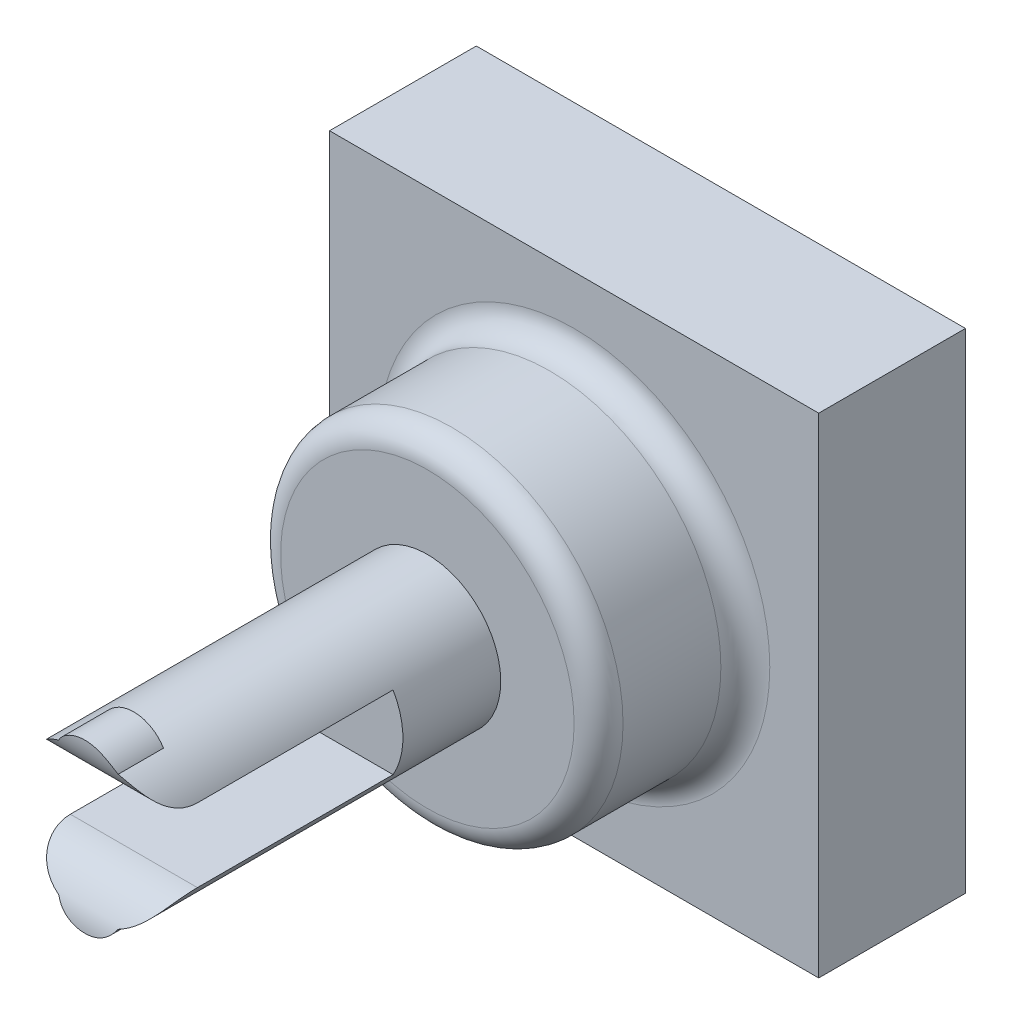
SolidWorks part; units mm, degrees
ref_plane "Plan de face" through (0, 0, 0) normal (0, 0, 1) x (1, 0, 0)
ref_plane "Plan de dessus" through (0, 0, 0) normal (0, 1, 0) x (1, 0, 0)
ref_plane "Plan de droite" through (0, 0, 0) normal (1, 0, 0) x (0, 0, -1)
sketch "Esquisse1" plane through (0, 0, 0) normal (0, 0, 1) x (1, 0, 0)
  line L1 (-5, -5) -> (5, -5)
  line L2 (-5, -5) -> (-5, 5)
  line L3 (-5, 5) -> (5, 5)
  line L4 (5, -5) -> (5, 5)
  line L5 (-5, -5) -> (5, 5) construction
  line L6 (-5, 5) -> (5, -5) construction
  point P0 (0, 0)
  dimension "D1" = 10
extrude "Boss.-Extru.1" add sketch "Esquisse1" along normal blind 3
sketch "Esquisse2" plane through (0, 0, 3) normal (0, 0, 1) x (1, 0, 0)
  line L0 (0, -5) -> (0, 5) construction
  line L1 (-5, -5) -> (5, -5) construction
  line L2 (5, 5) -> (-5, 5) construction
  circle A0 centre (0, 0) radius 3.5
  dimension "D1" = 7
extrude "Boss.-Extru.2" add sketch "Esquisse2" along normal blind 3
sketch "Esquisse5" plane through (0, 0, 6) normal (0, 0, 1) x (1, 0, 0)
  circle A0 centre (0, 0) radius 1.5
  dimension "D1" = 3
extrude "Boss.-Extru.4" add sketch "Esquisse5" along normal blind 7
sketch "Esquisse6" plane through (0, 0, 13) normal (0, 0, 1) x (1, 0, 0)
  line L0 (0, -1) -> (0, 1) construction
  line L1 (-0.7109, -1) -> (-0.7109, 1)
  line L2 (0.7109, -1) -> (0.7109, 1)
  line L3 (5, -5) -> (5, 5) construction
  arc A0 (-0.7109, -1) -> (0.7109, -1) centre (0, -1) ccw
  arc A1 (0.7109, 1) -> (-0.7109, 1) centre (0, 1) ccw
  point P2 (0, 0)
  dimension "D1" = 2
extrude "Boss.-Extru.5" add sketch "Esquisse6" against normal blind 1 contours L1 A1 L2 A0
sketch "Esquisse7" plane through (0, 0, 13) normal (0, 0, 1) x (1, 0, 0)
  line L0 (1.6241, 0) -> (-1.6241, 0) construction
  line L1 (1.6241, -0.75) -> (-1.6241, -0.75)
  line L2 (1.6241, 0.75) -> (-1.6241, 0.75)
  line L3 (5, 5) -> (-5, 5) construction
  arc A0 (1.6241, -0.75) -> (1.6241, 0.75) centre (1.6241, 0) ccw
  arc A1 (-1.6241, 0.75) -> (-1.6241, -0.75) centre (-1.6241, 0) ccw
  point P2 (0, 0)
  dimension "D1" = 1.5
extrude "Enlèv. mat.-Extru.1" cut sketch "Esquisse7" against normal blind 5
fillet "Congé1" radius 1 2 edges at (0, 0.75, 13) (0, -0.75, 13)
fillet "Congé5" radius 0.5 2 edges at (-3.5, 0, 3) (3.5, 0, 6)
